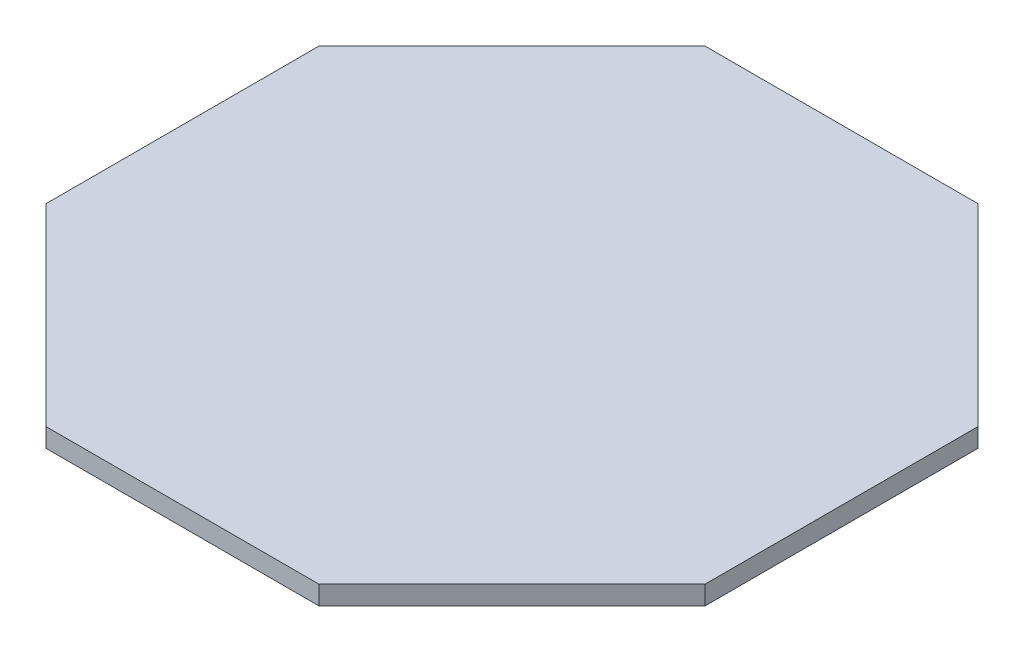
SolidWorks part; units mm, degrees
ref_plane "Front Plane" through (0, 0, 0) normal (0, 0, 1) x (1, 0, 0)
ref_plane "Top Plane" through (0, 0, 0) normal (0, 1, 0) x (1, 0, 0)
ref_plane "Right Plane" through (0, 0, 0) normal (1, 0, 0) x (0, 0, -1)
sketch "Sketch1" plane through (0, 0, 0) normal (0, 1, 0) x (1, 0, 0)
  line L0 (0, 0) -> (45.3198, 0) construction
  line L15 (0, 0) -> (38.2683, 15.8513) construction
  line L25 (35, 14.4975) -> (14.4975, 35)
  line L26 (14.4975, 35) -> (-14.4975, 35)
  line L27 (-14.4975, 35) -> (-35, 14.4975)
  line L28 (-35, 14.4975) -> (-35, -14.4975)
  line L29 (-35, -14.4975) -> (-14.4975, -35)
  line L30 (-14.4975, -35) -> (14.4975, -35)
  line L31 (14.4975, -35) -> (35, -14.4975)
  line L32 (35, -14.4975) -> (35, 14.4975)
  circle A0 centre (0, 0) radius 35 construction
  dimension "D1" = 35
extrude "Boss-Extrude1" add sketch "Sketch1" along normal blind 2
